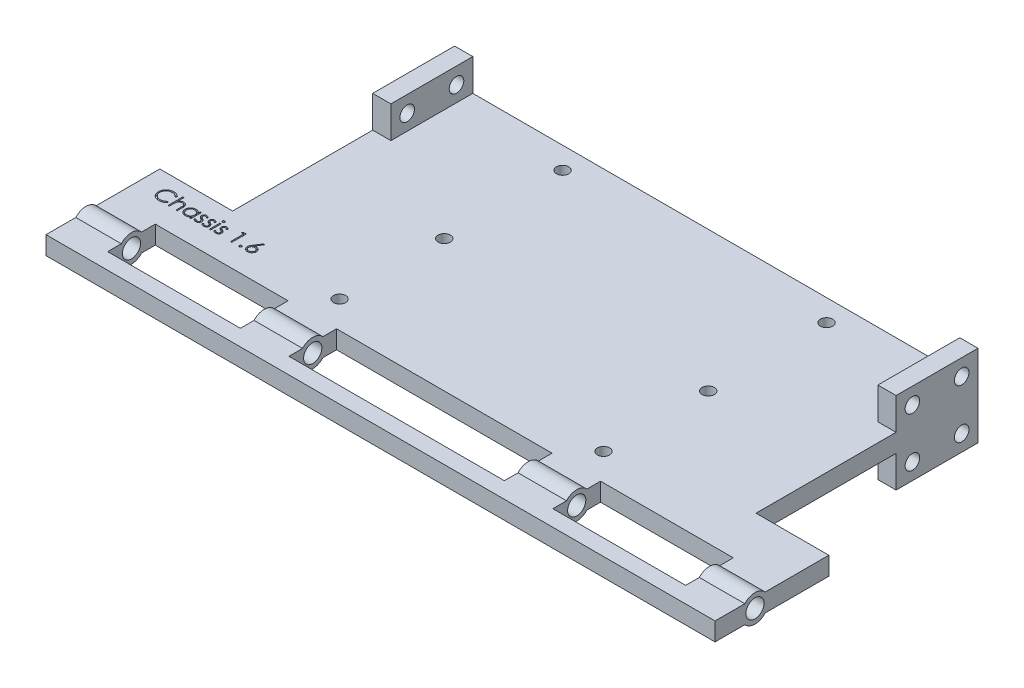
SolidWorks part; units mm, degrees
ref_plane "Front Plane" through (0, 0, 0) normal (0, 0, 1) x (1, 0, 0)
ref_plane "Top Plane" through (0, 0, 0) normal (0, 1, 0) x (1, 0, 0)
ref_plane "Right Plane" through (0, 0, 0) normal (1, 0, 0) x (0, 0, -1)
sketch "Sketch1" plane through (0, 0, 0) normal (0, 1, 0) x (1, 0, 0)
  line L0 (57.5, 0) -> (57.5, -73.7765) construction
  line L1 (0, 0) -> (115, 0)
  line L6 (57.5, -53.7765) -> (57.5, -73.7765) construction
  line L7 (28.5, -53.7765) -> (86.5, -53.7765) construction
  line L8 (28.5, -53.7765) -> (28.5, -30.7765) construction
  line L9 (28.5, -30.7765) -> (86.5, -30.7765) construction
  line L10 (86.5, -53.7765) -> (86.5, -30.7765) construction
  line L11 (28.5, -53.7765) -> (28.5, -4.7765) construction
  line L12 (28.5, -4.7765) -> (86.5, -4.7765) construction
  line L13 (86.5, -4.7765) -> (86.5, -53.7765) construction
  line L17 (0, -48.7765) -> (-16, -48.7765)
  line L18 (-16, -73.7765) -> (-16, -48.7765)
  line L19 (-16, -73.7765) -> (-16, 0) construction
  line L20 (-16, 0) -> (0, 0) construction
  line L21 (0, -48.7765) -> (0, 0)
  line L24 (131, -73.7765) -> (131, -48.7765)
  line L25 (131, -48.7765) -> (115, -48.7765)
  line L26 (115, -48.7765) -> (115, 0)
  line L27 (131, -73.7765) -> (-16, -73.7765)
  circle A0 centre (28.5, -30.7765) radius 1.35
  circle A1 centre (28.5, -53.7765) radius 1.35
  circle A2 centre (86.5, -30.7765) radius 1.35
  circle A3 centre (86.5, -53.7765) radius 1.35
  circle A4 centre (86.5, -4.7765) radius 1.35
  circle A5 centre (28.5, -4.7765) radius 1.35
  point P9 (57.5, 0)
  point P14 (57.5, -30.7765)
  point P16 (57.5, -53.7765)
  dimension "D5" = 2.7
  dimension "D6" = 2.7
  dimension "D9" = 2.7
  dimension "D10" = 2.7
  dimension "D11" = 2.7
  dimension "D12" = 2.7
  dimension "D1" = 115
  dimension "D2" = 48.7765
  dimension "D3" = 23
  dimension "D4" = 58
  dimension "D7" = 20
  dimension "D8" = 49
  dimension "D13" = 16
  dimension "D14" = 25
  dimension "D15" = 16
  dimension "D16" = 25
extrude "Base Chassis" add sketch "Sketch1" along normal mid plane 4
sketch "Sketch14" plane through (0, 2, 0) normal (0, 1, 0) x (1, 0, 0)
  text T0 "Chassis 1.6"
extrude "Text" cut sketch "Sketch14" against normal blind 0.5
sketch "Sketch7" plane through (0, 0, 0) normal (-1, 0, 0) x (0, 0, 1)
  line L12 (0, -9) -> (0, 9)
  line L13 (0, 9) -> (18, 9)
  line L15 (0, -2) -> (73.7765, -2) construction
  line L23 (0, -9) -> (18, 9) construction
  line L24 (9, 0) -> (3.5828, 5.4172) construction
  line L28 (0, -9) -> (18, -9)
  line L35 (18, -9) -> (18, 9)
  line L36 (0, 0) -> (9, 0) construction
  line L37 (9, 0) -> (9, -9) construction
  circle A4 centre (9, 0) radius 7.661 construction
  circle A5 centre (3.5828, 5.4172) radius 1.6
  circle A9 centre (14.4172, 5.4172) radius 1.6
  circle A10 centre (14.4172, -5.4172) radius 1.6
  circle A11 centre (3.5828, -5.4172) radius 1.6
  point P1 (0, 0)
  point P2 (0, 0)
  point P24 (9, 0)
  dimension "D3" = 15.322
  dimension "D4" = 3.2
  dimension "D5" = 9
  dimension "D1" = 18
  dimension "D6" = 9
extrude "Mount Holes" add sketch "Sketch7" against normal blind 4
sketch "Sketch8" plane through (-16, 0, 0) normal (-1, 0, 0) x (0, 0, 1)
  line L0 (9, 9) -> (9, -9) construction
  line L1 (18, 9) -> (0, 9) construction
  line L3 (65, 3) -> (65, -3) construction
  line L6 (9, 0) -> (65, 0) construction
  line L7 (0, -9) -> (18, -9) construction
  circle A0 centre (65, 0) radius 3
  dimension "D2" = 6
  dimension "D1" = 56
extrude "Shaft Extrude" add sketch "Sketch8" against normal through all
sketch "Sketch20" plane through (-16, 0, 0) normal (-1, 0, 0) x (0, 0, 1)
  circle A0 centre (65, 0) radius 2
  dimension "D1" = 4
extrude "Shaft Cut" cut sketch "Sketch20" against normal through all
sketch "Sketch10" plane through (0, 2, 0) normal (0, 1, 0) x (1, 0, 0)
  line L0 (57.5, 0) -> (57.5, -73.7765) construction
  line L1 (115, 0) -> (4, 0) construction
  line L2 (0, -73.7765) -> (115, -73.7765) construction
  line L3 (-16, -65) -> (57.5, -65) construction
  line L5 (-6, -65) -> (-6, -62.7639)
  line L11 (115, -73.7765) -> (115, -66.2361) construction
  line L19 (-6, -62.7639) -> (-6, -59.7639)
  line L20 (-6, -59.7639) -> (23.1719, -59.7639)
  line L21 (23.1719, -59.7639) -> (23.1719, -62.7639)
  line L22 (23.1719, -62.7639) -> (23.1719, -65)
  line L23 (23.1719, -65) -> (23.1719, -67.2361)
  line L24 (23.1719, -70.2361) -> (33.8281, -70.2361) construction
  line L25 (23.1719, -67.2361) -> (23.1719, -70.2361)
  line L26 (23.1719, -70.2361) -> (-6, -70.2361)
  line L27 (-6, -70.2361) -> (-6, -67.2361)
  line L28 (-6, -67.2361) -> (-6, -65)
  line L29 (-16, -73.7765) -> (-6, -73.7765) construction
  line L30 (-6, -73.7765) -> (-6, -70.2361) construction
  line L31 (23.1719, -59.7639) -> (33.8281, -59.7639) construction
  line L32 (33.8281, -59.7639) -> (33.8281, -62.7639)
  line L33 (33.8281, -62.7639) -> (33.8281, -65)
  line L34 (33.8281, -65) -> (33.8281, -67.2361)
  line L35 (33.8281, -67.2361) -> (33.8281, -70.2361)
  line L36 (33.8281, -70.2361) -> (57.5, -70.2361)
  line L37 (57.5, -70.2361) -> (57.5, -67.2361)
  line L38 (57.5, -67.2361) -> (57.5, -65)
  line L39 (57.5, -65) -> (57.5, -62.7639)
  line L40 (57.5, -62.7639) -> (57.5, -59.7639)
  line L41 (57.5, -59.7639) -> (33.8281, -59.7639)
  line L42 (-16, -73.7765) -> (131, -73.7765) construction
  line L44 (131, -67.2361) -> (-16, -67.2361) construction
  line L46 (-16, -62.7639) -> (-16, -67.2361) construction
  line L47 (-16, -62.7639) -> (131, -62.7639) construction
  dimension "D1" = 3
  dimension "D2" = 3
  dimension "D3" = 10.6562
  dimension "D4" = 10
  dimension "D6" = 23.6719
extrude "Screw Hole" cut sketch "Sketch10" against normal through all both and the other way through all contours L40 L41 L32 L33 L34 L35 L36 L37 L38 L39 | L25 L26 L27 L28 L5 L19 L20 L21 L22 L23 region at (45.664, 2, 65)
ref_plane "Plane1" through (57.5, 0, 0) normal (-1, 0, 0) x (0, 0, 1)
mirror "Mirror1" about plane through (57.5, 0, 0) normal (-1, 0, 0) of "Screw Hole", "Mount Holes"
ref_plane "Plane2" through (1.1976, 2, 52.5005) normal (0, 0, 1) x (1, 0, 0)
